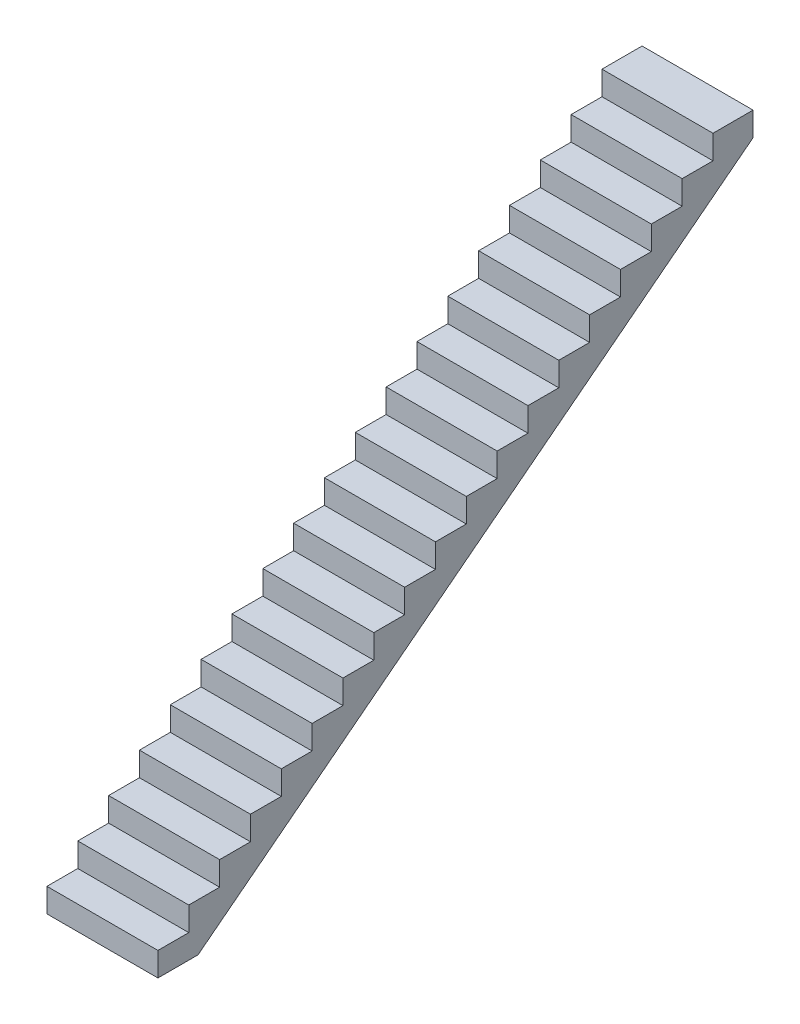
SolidWorks part; units mm, degrees
ref_plane "Front Plane" through (0, 0, 0) normal (0, 0, 1) x (1, 0, 0)
ref_plane "Top Plane" through (0, 0, 0) normal (0, 1, 0) x (1, 0, 0)
ref_plane "Right Plane" through (0, 0, 0) normal (1, 0, 0) x (0, 0, -1)
sketch "Sketch1" plane through (0, 0, 0) normal (1, 0, 0) x (0, 0, -1)
  line L1 (0, 0) -> (254, 0)
  line L2 (0, 0) -> (0, 196.85)
  line L3 (0, 196.85) -> (254, 196.85)
  line L4 (254, 0) -> (254, 196.85)
  dimension "D1" = 196.85
  dimension "D2" = 254
extrude "ModelStep" add sketch "Sketch1" along normal mid plane 914.4
ref_axis "stairsAxis" through (0, 0, 0) along (0, 0.6126, -0.7904)
ref_plane "MaxVerticalRise" through (0, 3835.4, 0) normal (0, 1, 0) x (1, 0, 0)
sketch "Sketch4" plane through (0, 0, -254) normal (0, 0, -1) x (-1, 0, 0)
  line L8 (457.2, 0) -> (457.2, 196.85)
  line L9 (457.2, 196.85) -> (-457.2, 196.85)
  line L10 (-457.2, 196.85) -> (-457.2, 0)
  line L11 (-457.2, 0) -> (457.2, 0)
  line L12 (457.2, 0) -> (457.2, 196.85)
  line L13 (457.2, 196.85) -> (-457.2, 196.85)
  line L14 (-457.2, 196.85) -> (-457.2, 0)
  line L15 (-457.2, 0) -> (457.2, 0)
  dimension "D1" = 0
extrude "ExtrudeMaxStairWidth" add sketch "Sketch4" along normal blind 76.2
ref_point "Collision with max vertical rise"
pattern_linear "Pattern stairs" count 19 spacing 321.3502 along (0, 0.6126, -0.7904) of "ModelStep", "ExtrudeMaxStairWidth"
ref_plane "CombineStairsSketchPlane" through (0, -159.8782, -123.9056) normal (0, -0.7904, -0.6126) x (-1, 0, 0)
sketch "Sketch5" plane through (0, -159.8782, -123.9056) normal (0, -0.7904, -0.6126) x (-1, 0, 0)
  line L1 (-457.2, 6045.2979) -> (457.2, 6045.2979)
  line L2 (-457.2, 6045.2979) -> (-457.2, 260.9951)
  line L3 (-457.2, 260.9951) -> (457.2, 260.9951)
  line L4 (457.2, 6045.2979) -> (457.2, 260.9951)
extrude "CombineStairs" add sketch "Sketch5" against normal up to vertex (202.2712 mm away) up to point (457.2, 1968.5, -2540)
equation "\"GreatestVerticalRiserHeight\"= 7.75"
equation "\"D1@Sketch1\"=\"GreatestVerticalRiserHeight\""
equation "\"MinimumTreadDepth\"=10"
equation "\"D2@Sketch1\"=\"MinimumTreadDepth\""
equation "\"D3@Pattern stairs\"=(\"D2@Sketch1\"^2 + \"D1@Sketch1\"^2)^0.5"
